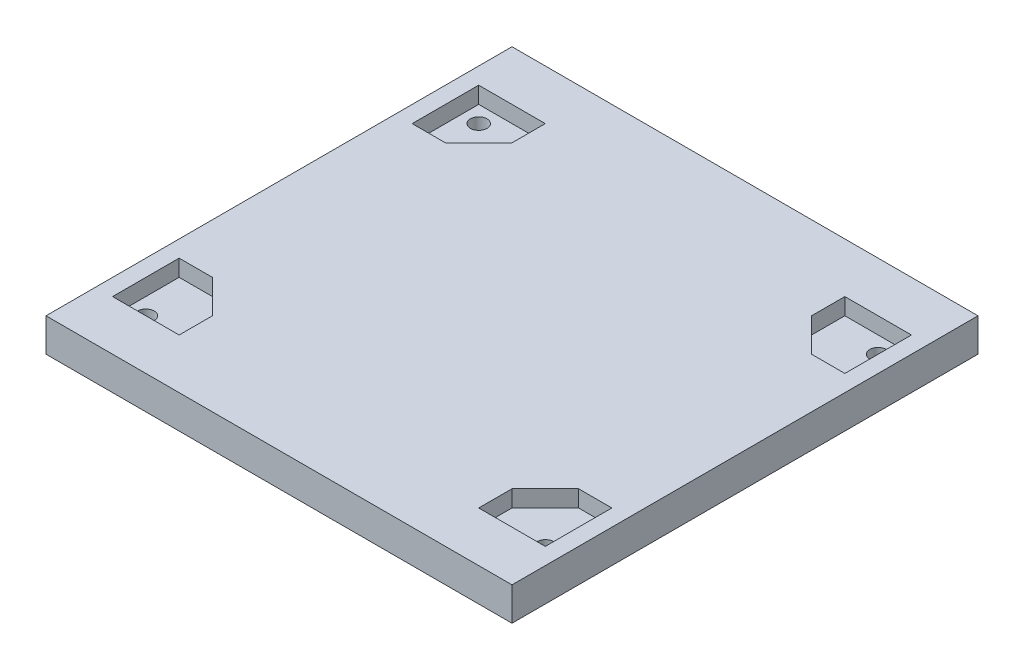
SolidWorks part; units mm, degrees
ref_plane "Front Plane" through (0, 0, 0) normal (0, 0, 1) x (1, 0, 0)
ref_plane "Top Plane" through (0, 0, 0) normal (0, 1, 0) x (1, 0, 0)
ref_plane "Right Plane" through (0, 0, 0) normal (1, 0, 0) x (0, 0, -1)
sketch "Sketch1" plane through (0, 0, 0) normal (0, 1, 0) x (1, 0, 0)
  line L1 (0, 0) -> (84, 0)
  line L2 (0, 0) -> (0, 84)
  line L3 (0, 84) -> (84, 84)
  line L4 (84, 0) -> (84, 84)
  dimension "D1" = 84
  dimension "D2" = 84
extrude "Boss-Extrude1" add sketch "Sketch1" along normal blind 6
sketch "Sketch2" plane through (0, 6, 0) normal (0, 1, 0) x (1, 0, 0)
  line L0 (84, 84) -> (0, 84) construction
  line L1 (0, 84) -> (0, 0) construction
  line L2 (0, 0) -> (84, 0) construction
  line L3 (84, 0) -> (84, 84) construction
  circle A0 centre (6, 72) radius 1.5
  circle A1 centre (6, 12) radius 1.5
  circle A2 centre (78, 12) radius 1.5
  circle A3 centre (78, 72) radius 1.5
  dimension "D1" = 3
  dimension "D2" = 3
  dimension "D3" = 3
  dimension "D4" = 3
  dimension "D6" = 6
  dimension "D7" = 12
  dimension "D8" = 6
  dimension "D9" = 6
  dimension "D10" = 12
  dimension "D11" = 6
  dimension "D5" = 12
  dimension "D12" = 12
extrude "Cut-Extrude1" cut sketch "Sketch2" against normal through all
ref_plane "Plane1" through (0, 0, -42) normal (0, 0, 1) x (1, 0, 0)
sketch "Sketch4" plane through (0, 6, 0) normal (0, 1, 0) x (1, 0, 0)
  line L0 (3, 21) -> (3, 9)
  line L1 (3, 9) -> (15, 9)
  line L2 (15, 15) -> (9, 21)
  line L3 (3, 21) -> (9, 21)
  line L4 (9, 21) -> (15, 15)
  line L5 (15, 15) -> (15, 9)
  line L6 (0, 84) -> (0, 0) construction
  line L7 (0, 0) -> (84, 0) construction
  circle A0 centre (6, 12) radius 1.5
  circle A1 centre (6, 12) radius 1.5 construction
  circle M21 centre (6, 12) radius 1.5
  dimension "D1" = 3
  dimension "D2" = 9
  dimension "D3" = 12
  dimension "D4" = 12
  dimension "D5" = 6
  dimension "D6" = 6
extrude "Cut-Extrude4" cut sketch "Sketch4" against normal blind 3 contours L5 L2 L3 L0 L1 M21 region at (8.5729, 6, -14.5729)
mirror "Mirror2" about plane through (0, 0, -42) normal (0, 0, 1) of "Cut-Extrude4"
ref_plane "Plane2" through (42, 0, 0) normal (-1, 0, 0) x (0, 0, 1)
mirror "Mirror3" about plane through (42, 0, 0) normal (-1, 0, 0) of "Mirror2"
